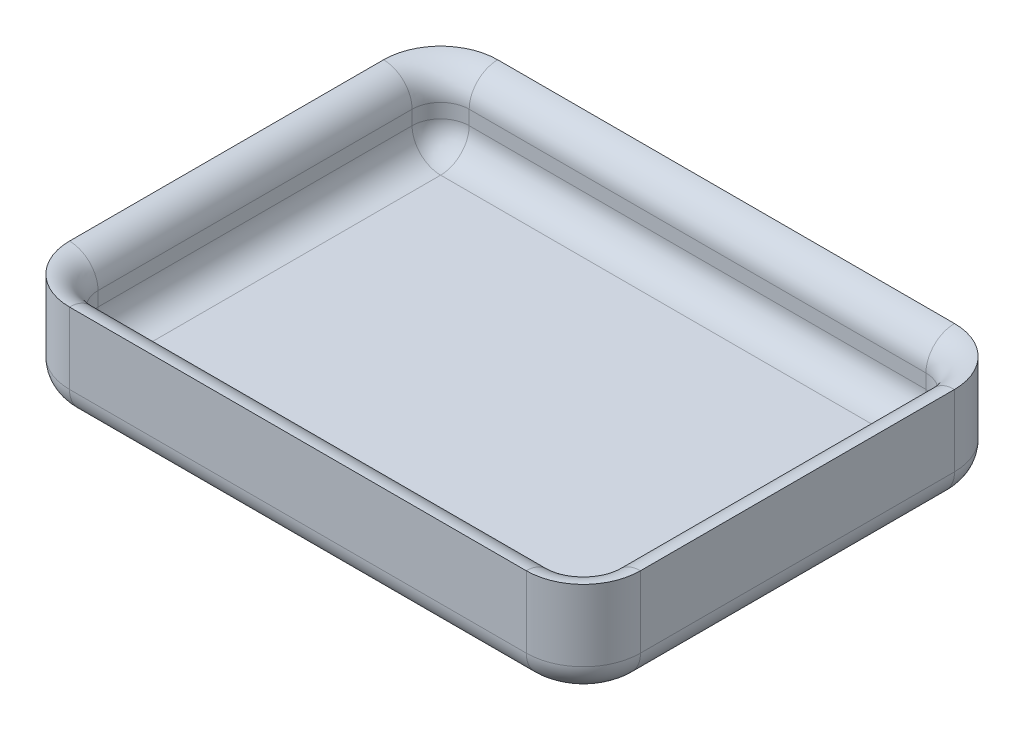
SolidWorks part; units mm, degrees
ref_plane "Plan de face" through (0, 0, 0) normal (0, 0, 1) x (1, 0, 0)
ref_plane "Plan de dessus" through (0, 0, 0) normal (0, 1, 0) x (1, 0, 0)
ref_plane "Plan de droite" through (0, 0, 0) normal (1, 0, 0) x (0, 0, -1)
sketch "Esquisse1" plane through (0, 0, 0) normal (0, 1, 0) x (1, 0, 0)
  line L1 (-16, -15) -> (16, -15)
  line L2 (-20, -11) -> (-20, 11)
  line L3 (-16, 15) -> (16, 15)
  line L4 (20, -11) -> (20, 11)
  arc A0 (-16, -15) -> (-20, -11) centre (-16, -11) cw
  arc A1 (16, -15) -> (20, -11) centre (16, -11) ccw
  arc A2 (16, 15) -> (20, 11) centre (16, 11) cw
  arc A3 (-20, 11) -> (-16, 15) centre (-16, 11) cw
  point P4 (0, 0)
  point P8 (-20, -15)
  point P11 (20, -15)
  point P14 (20, 15)
  point P17 (-20, 15)
  dimension "D5" = 4
  dimension "D1" = 20
  dimension "D2" = 40
  dimension "D3" = 15
  dimension "D4" = 30
extrude "Boss.-Extru.1" add sketch "Esquisse1" along normal blind 7
sketch "Esquisse2" plane through (0, 7, 0) normal (0, 1, 0) x (1, 0, 0)
  line L8 (18, -11) -> (18, 11)
  line L9 (-16, -13) -> (16, -13)
  line L10 (-18, 11) -> (-18, -11)
  line L11 (16, 13) -> (-16, 13)
  line L12 (18, -11) -> (18, 11)
  line L13 (-16, -13) -> (16, -13)
  line L14 (-18, 11) -> (-18, -11)
  line L15 (16, 13) -> (-16, 13)
  arc A8 (18, 11) -> (16, 13) centre (16, 11) ccw
  arc A9 (16, -13) -> (18, -11) centre (16, -11) ccw
  arc A10 (-18, -11) -> (-16, -13) centre (-16, -11) ccw
  arc A11 (-16, 13) -> (-18, 11) centre (-16, 11) ccw
  arc A12 (18, 11) -> (16, 13) centre (16, 11) ccw
  arc A13 (16, -13) -> (18, -11) centre (16, -11) ccw
  arc A14 (-18, -11) -> (-16, -13) centre (-16, -11) ccw
  arc A15 (-16, 13) -> (-18, 11) centre (-16, 11) ccw
  dimension "D1" = 2
extrude "Enlèv. mat.-Extru.1" cut sketch "Esquisse2" against normal blind 5
fillet "Congé1" radius 2 8 edges at (17.4142, 2, 12.4142) (0, 2, 13) (-17.4142, 2, 12.4142) (-18, 2, 0) (-17.4142, 2, -12.4142) (18, 2, 0) (17.4142, 2, -12.4142) (0, 2, -13)
fillet "Congé2" radius 2 8 edges at (-18.8284, 0, 13.8284) (-20, 0, 0) (-18.8284, 0, -13.8284) (0, 0, -15) (18.8284, 0, -13.8284) (20, 0, 0) (18.8284, 0, 13.8284) (0, 0, 15)
fillet "Congé3" radius 2 8 edges at (17.4142, 7, 12.4142) (0, 7, 13) (-17.4142, 7, 12.4142) (-18, 7, 0) (-17.4142, 7, -12.4142) (0, 7, -13) (17.4142, 7, -12.4142) (18, 7, 0)
